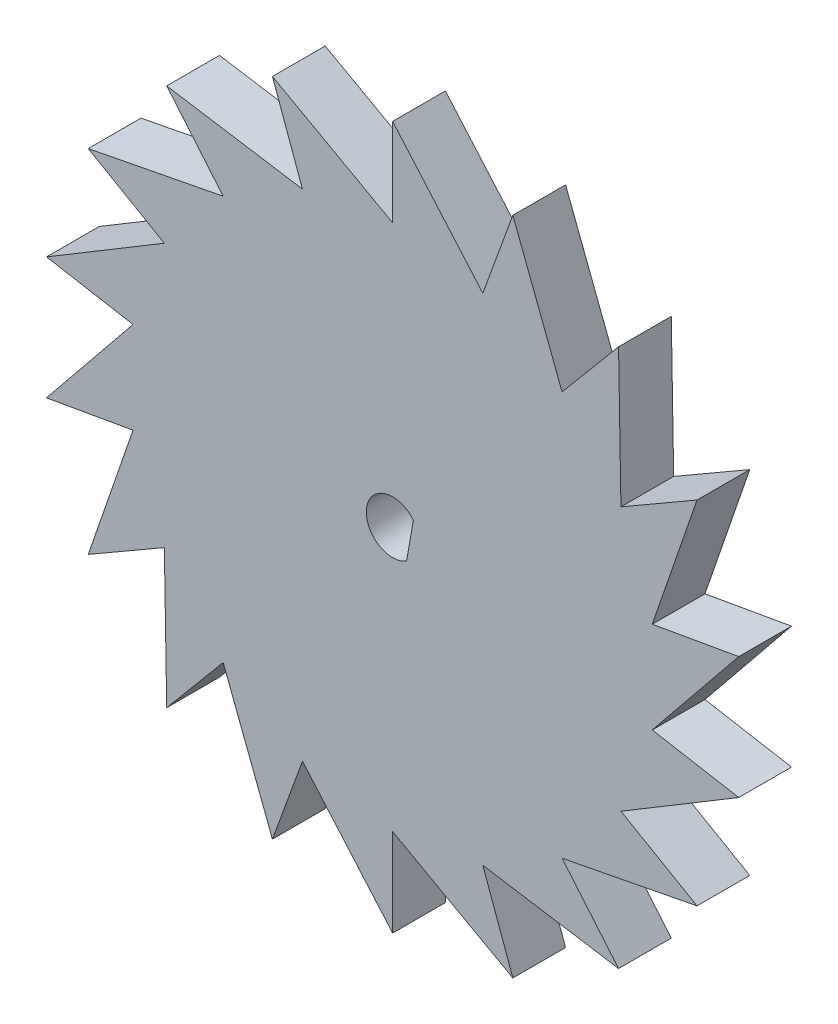
SolidWorks part; units mm, degrees
ref_plane "Front Plane" through (0, 0, 0) normal (0, 0, 1) x (1, 0, 0)
ref_plane "Top Plane" through (0, 0, 0) normal (0, 1, 0) x (1, 0, 0)
ref_plane "Right Plane" through (0, 0, 0) normal (1, 0, 0) x (0, 0, -1)
sketch "Sketch1" plane through (0, 0, 0) normal (0, 0, 1) x (1, 0, 0)
  line L0 (0, 0) -> (0, 20)
  line L3 (5.1303, 14.0954) -> (0, 0)
  line L4 (5.1303, 14.0954) -> (0, 20)
  dimension "D1" = 20
  dimension "D2" = 15
  dimension "D3" = 20
extrude "Boss-Extrude1" add sketch "Sketch1" along normal blind 3
pattern_circular "CirPattern1" count 18 every 20 about axis through (0, 0, 3) along (0, 0, -1) of "Boss-Extrude1" reverse direction yes
sketch "Sketch2" plane through (0, 0, 3) normal (0, 0, 1) x (1, 0, 0)
  line L0 (1.3896, 2.1214) -> (0.6326, -2.1704)
  circle A0 centre (0, 0) radius 1.5
  dimension "D1" = 3
  dimension "D2" = 1
sketch "Sketch5" plane through (0, 0, 3) normal (0, 0, 1) x (1, 0, 0)
  line L0 (1.179, 0.9273) -> (0.7906, -1.2747)
  line L1 (1.3896, 2.1214) -> (0.6326, -2.1704) construction
  arc A1 (0.7906, -1.2747) -> (1.179, 0.9273) centre (0, 0) cw
extrude "Cut-Extrude1" cut sketch "Sketch5" against normal blind 3
